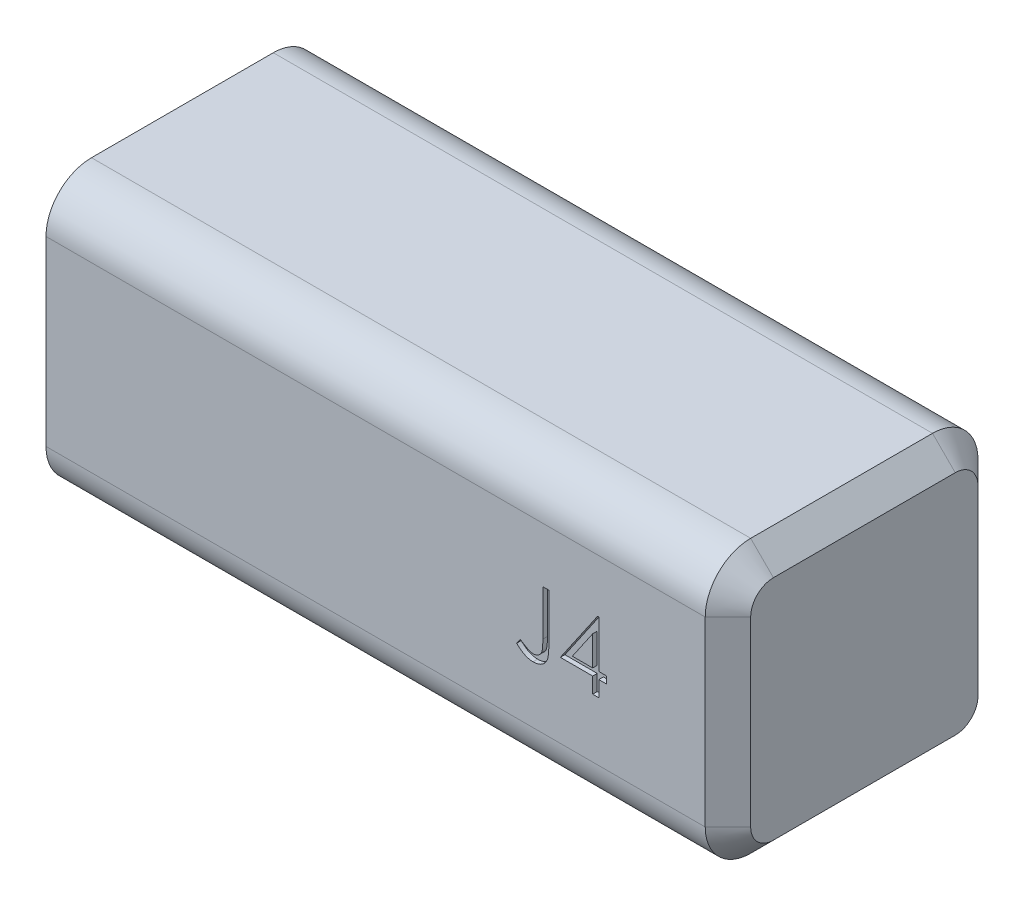
SolidWorks part; units mm, degrees
ref_plane "Alzado" through (0, 0, 0) normal (0, 0, 1) x (1, 0, 0)
ref_plane "Planta" through (0, 0, 0) normal (0, 1, 0) x (1, 0, 0)
ref_plane "Vista lateral" through (0, 0, 0) normal (1, 0, 0) x (0, 0, -1)
sketch "Sketch1" plane through (0, 0, 0) normal (0, 0, 1) x (1, 0, 0)
  line L1 (-75, -30) -> (75, -30)
  line L2 (-75, -30) -> (-75, 30)
  line L3 (-75, 30) -> (75, 30)
  line L4 (75, -30) -> (75, 30)
  line L5 (-75, -30) -> (75, 30) construction
  line L6 (-75, 30) -> (75, -30) construction
  point P0 (0, 0)
  dimension "D1" = 60
  dimension "D2" = 150
extrude "Boss-Extrude1" add sketch "Sketch1" along normal blind 30 and the other way blind 30
fillet "Fillet1" radius 10 4 edges at (0, -30, -30) (0, -30, 30) (0, 30, 30) (0, 30, -30)
chamfer "Chamfer1" distance 5 angle 45 8 edges at (75, -30, 0) (75, -27.0711, -27.0711) (75, -27.0711, 27.0711) (75, 0, -30) (75, 0, 30) (75, 27.0711, -27.0711) (75, 27.0711, 27.0711) (75, 30, 0)
sketch "Sketch4" plane through (0, 0, 30) normal (0, 0, 1) x (1, 0, 0)
  text T0 "J4" font "Century Gothic" height 15
extrude "Cut-Extrude1" cut sketch "Sketch4" against normal blind 1
sketch "Sketch14" plane through (-75, 0, 0) normal (-1, 0, 0) x (0, 0, 1)
  circle A7 centre (0, 0) radius 22.5
extrude "Cut-Extrude5" cut sketch "Sketch14" against normal blind 100
